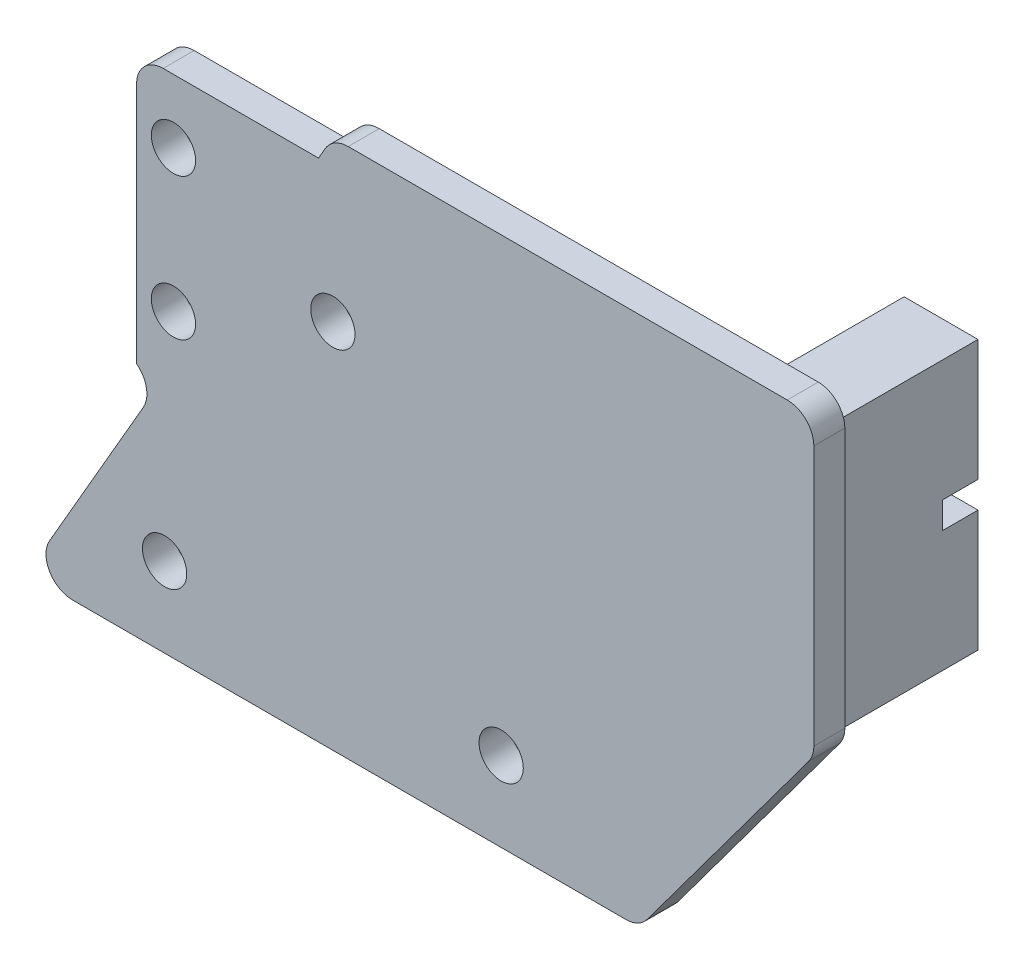
SolidWorks part; units mm, degrees
ref_plane "Front Plane" through (0, 0, 0) normal (0, 0, 1) x (1, 0, 0)
ref_plane "Top Plane" through (0, 0, 0) normal (0, 1, 0) x (1, 0, 0)
ref_plane "Right Plane" through (0, 0, 0) normal (1, 0, 0) x (0, 0, -1)
sketch "Sketch1" plane through (0, 0, 0) normal (0, 0, 1) x (1, 0, 0)
  line L0 (-32.7569, -9) -> (36.42, -9)
  line L1 (36.42, -9) -> (56.1366, 17.5709)
  line L2 (1.8315, 50.909) -> (-32.7569, -9)
  line L3 (56.1366, 17.5709) -> (56.1366, 50.909)
  line L4 (56.1366, 50.909) -> (1.8315, 50.909)
  circle A0 centre (-17.1685, 0) radius 2.5
  circle A1 centre (20.8315, 0) radius 2.5
  circle A2 centre (1.8315, 32.909) radius 2.5
  point P6 (50.9989, 14.1919)
  point P12 (54.6441, 16.9258)
  point P13 (0, 0)
  point P14 (56.1366, 17.5709)
  dimension "D5" = 5
  dimension "D1" = 38
  dimension "D2" = 38
  dimension "D3" = 38
  dimension "D4" = 9
  dimension "D6" = 9
extrude "Boss-Extrude1" add sketch "Sketch1" along normal blind 3.5
fillet "Fillet1" radius 3 3 edges at (-32.7569, -9, 1.75) (1.8315, 50.909, 1.75) (36.42, -9, 1.75)
sketch "Sketch2" plane through (0, 0, 0) normal (0, 0, -1) x (-1, 0, 0)
  line L0 (-55.1719, 32.909) -> (20.3281, 32.909) construction
  line L1 (-55.1719, 48.1) -> (20.3281, 48.1)
  line L2 (-55.1719, 48.1) -> (-55.1719, 17.718)
  line L3 (-55.1719, 17.718) -> (20.3281, 17.718)
  line L4 (20.3281, 48.1) -> (20.3281, 17.718)
  line L5 (-55.1719, 48.1) -> (20.3281, 17.718) construction
  line L6 (-55.1719, 17.718) -> (20.3281, 48.1) construction
  line L7 (-46.8315, 48.1) -> (-46.8315, 17.718)
  line L8 (12.1685, 48.1) -> (12.1685, 17.718)
  line L9 (16.1685, 48.1) -> (16.1685, 17.718) construction
  line L10 (-50.8315, 48.1) -> (-50.8315, 17.718) construction
  line L11 (12.1685, 34.409) -> (20.3281, 34.409)
  line L12 (20.3281, 34.409) -> (20.3281, 31.409)
  line L13 (20.3281, 31.409) -> (12.1685, 31.409)
  line L14 (-46.8315, 34.409) -> (-55.1719, 34.409)
  line L15 (-46.8315, 31.409) -> (-55.1719, 31.409)
  line L16 (-46.8315, 48.1) -> (12.1685, 17.718) construction
  line L17 (12.1685, 17.718) -> (12.1685, 48.1) construction
  line L18 (12.1685, 48.1) -> (-46.8315, 17.718) construction
  circle A0 centre (-1.8315, 32.909) radius 4.125
  circle A1 centre (16.1685, 40.909) radius 2.5
  circle A2 centre (16.1685, 24.909) radius 2.5
  circle A3 centre (-50.8315, 24.909) radius 2.5
  circle A4 centre (-50.8315, 40.909) radius 2.5
  point P0 (-17.4219, 32.909)
  point P26 (-17.3315, 32.909)
  dimension "D2" = 8.25
  dimension "D12" = 5
  dimension "D1" = 75.5
  dimension "D3" = 14
  dimension "D4" = 45
  dimension "D5" = 67
  dimension "D6" = 3
  dimension "D7" = 1.5
  dimension "D8" = 3
  dimension "D9" = 4
  dimension "D10" = 4
  dimension "D11" = 59
  dimension "D13" = 16
  dimension "D14" = 16
  dimension "D15" = 8
  dimension "D16" = 8
extrude "Boss-Extrude2" add sketch "Sketch2" against normal blind 3.5 contours A4 | A3 | A2 | A1 | L1 L4 L3 L2 | A0 region at (-16.1685, 40.909, 0) region at (-16.1685, 24.909, 0) region at (50.8315, 24.909, 0) region at (50.8315, 40.909, 0)
extrude "Boss-Extrude3" add sketch "Sketch2<4>" along normal blind 16 contours L14 L7 L1 L2 A4 | L7 L15 L2 L3 A3 region at (51.0017, 47.9397, 0) region at (51.0017, 31.2487, 0)
sketch "Sketch2<4>" plane through (0, 0, 0) normal (0, 0, -1) x (-1, 0, 0) same geometry as "Sketch2"
fillet "Fillet2" radius 3 1 edges at (-17.3313, 17.718, 1.75)
fillet "Fillet3" radius 3 3 edges at (-20.3281, 48.1, 1.75) (56.1366, 17.5709, 1.75) (56.1366, 50.909, 1.75)
extrude "Boss-Extrude5" add sketch "Sketch2<7>" along direction (0, 0, -1) on the side of the normal offset from surface (12 mm away) 4 contours L15 L7 L14 L2 region at (51.0017, 32.909, 0) up to face at (48.3315, 24.909, -16)
sketch "Sketch2<7>" plane through (0, 0, 0) normal (0, 0, -1) x (-1, 0, 0) same geometry as "Sketch2"
equation "\"D2@Sketch1\"=\"D1@Sketch1\""
equation "\"D3@Sketch1\"=\"D1@Sketch1\""
equation "\"D6@Sketch1\"=\"D4@Sketch1\""
equation "\"D7@Sketch2\"=\"D6@Sketch2\"/2"
equation "\"D8@Sketch2\"=3"
